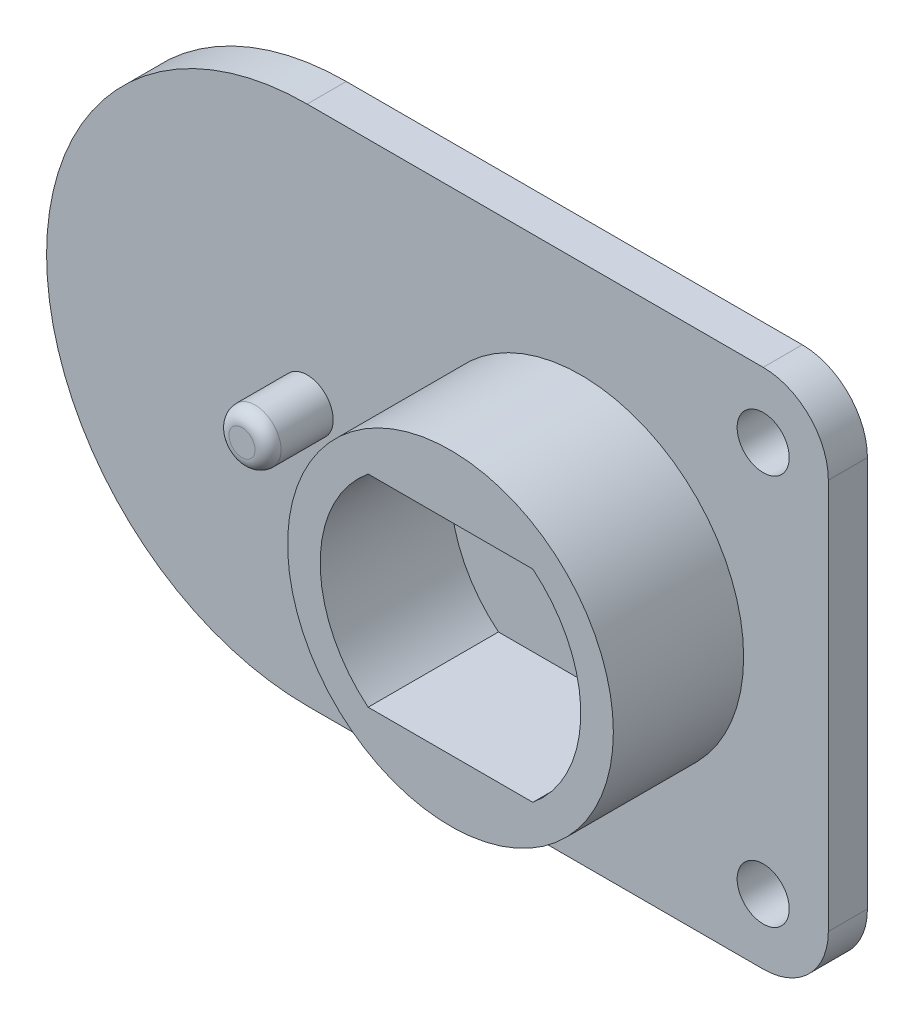
SolidWorks part; units mm, degrees
ref_plane "Ebene vorne" through (0, 0, 0) normal (0, 0, 1) x (1, 0, 0)
ref_plane "Ebene oben" through (0, 0, 0) normal (0, 1, 0) x (1, 0, 0)
ref_plane "Ebene rechts" through (0, 0, 0) normal (1, 0, 0) x (0, 0, -1)
sketch "Skizze1" plane through (0, 0, 0) normal (0, 0, 1) x (1, 0, 0)
  line L0 (0, 20) -> (40, 20)
  line L1 (0, -20) -> (40, -20)
  line L2 (40, 20) -> (40, -20)
  line L3 (0, 0) -> (40, 0) construction
  circle A0 centre (0, 0) radius 20
  circle A1 centre (0, 0) radius 1
  circle A2 centre (21, 0) radius 1.5
  circle A3 centre (35, -15) radius 2
  circle A4 centre (35, 15) radius 2
  dimension "D1" = 40
  dimension "D2" = 2
  dimension "D4" = 3
  dimension "D8" = 4
  dimension "D3" = 40
  dimension "D5" = 21
  dimension "D6" = 5
  dimension "D7" = 5
extrude "Aufsatz-Linear austragen1" add sketch "Skizze1" along normal blind 3 contours A1 A2 A0 | L3 A2 A0 L1 L2 | A2 L3 L2 L0 A0 region at (13.3623, 14.112, 0) region at (27.2842, 10.9393, 0) region at (27.2842, -10.9393, 0)
fillet "Verrundung1" radius 5 2 edges at (40, -20, 1.5) (40, 20, 1.5)
sketch "Skizze2" plane through (0, 0, 3) normal (0, 0, 1) x (1, 0, 0)
  line L0 (14.6804, 7.75) -> (27.3196, 7.75)
  line L1 (27.3196, -7.75) -> (14.6804, -7.75)
  line L2 (21, -7.75) -> (21, 7.75)
  circle A0 centre (21, 0) radius 12.5
  circle A1 centre (21, 0) radius 10
  circle A2 centre (21, 0) radius 1.5 construction
  point P10 (0, 0)
  dimension "D2" = 20
  dimension "D3" = 25
  dimension "D4" = 3
  dimension "D1" = 15.5
extrude "Aufsatz-Linear austragen2" add sketch "Skizze2" along normal blind 10 contours A0 A1 | L1 A1 | L0 A1 region at (21, 8.6593, 3) region at (21, -8.6593, 3) region at (8.8536, 0, 3)
sketch "Skizze3" plane through (0, 0, 3) normal (0, 0, 1) x (1, 0, 0)
  circle A0 centre (0, 0) radius 2
  dimension "D1" = 4
extrude "Aufsatz-Linear austragen3" add sketch "Skizze3" along normal blind 5
fillet "Verrundung2" radius 1 1 edges at (2, 0, 8)
